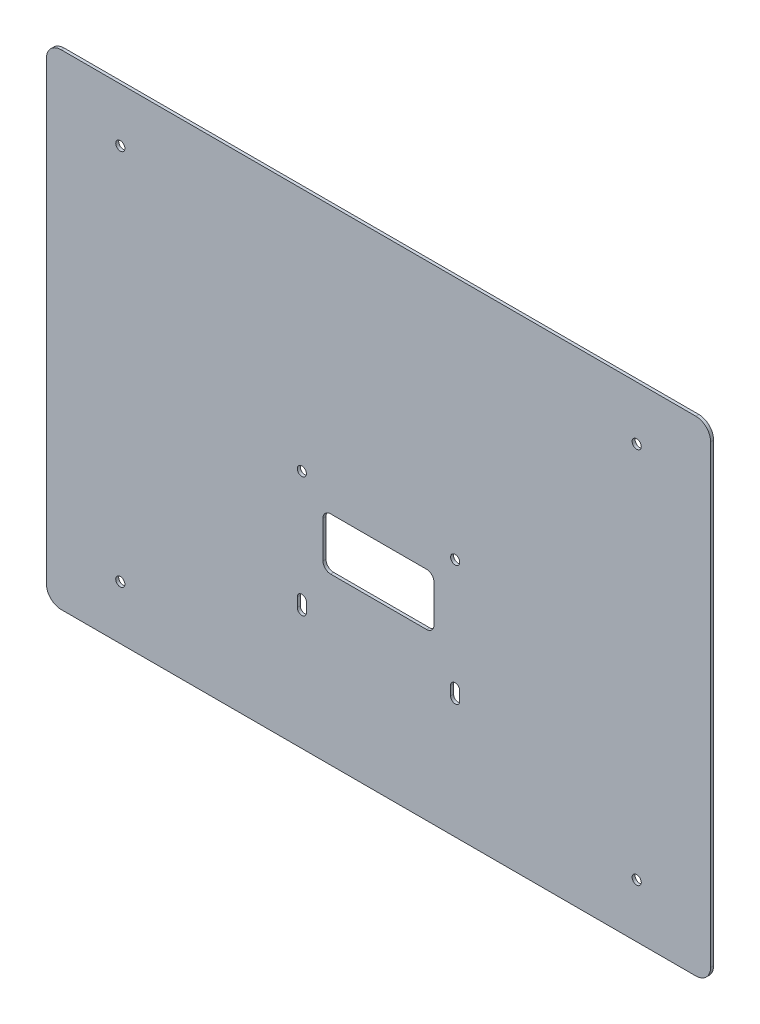
SolidWorks part; units mm, degrees
ref_plane "Front Plane" through (0, 0, 0) normal (0, 0, 1) x (1, 0, 0)
ref_plane "Top Plane" through (0, 0, 0) normal (0, 1, 0) x (1, 0, 0)
ref_plane "Right Plane" through (0, 0, 0) normal (1, 0, 0) x (0, 0, -1)
sketch "Sketch2" plane through (0, 0, 0) normal (0, 0, 1) x (1, 0, 0)
  line L1 (-225.24, 164.41) -> (225.24, 164.41)
  line L2 (-225.24, 164.41) -> (-225.24, -164.41)
  line L3 (-225.24, -164.41) -> (225.24, -164.41)
  line L4 (225.24, 164.41) -> (225.24, -164.41)
  line L5 (-225.24, 164.41) -> (225.24, -164.41) construction
  line L6 (-225.24, -164.41) -> (225.24, 164.41) construction
  point P0 (0, 0)
  dimension "Length 1" = 450.48
  dimension "Length 2" = 328.82
extrude "Boss-Extrude1" add sketch "Sketch2" along normal blind 2.032
sketch "Sketch3" plane through (0, 0, 2.032) normal (0, 0, 1) x (1, 0, 0)
  circle A0 centre (-175.117, 128.01) radius 3.1
  circle A1 centre (175.117, 128.01) radius 3.1
  circle A8 centre (-175.1171, -128.01) radius 3.1
  circle A9 centre (175.1169, -128.01) radius 3.1
  dimension "D1" = 6.2
extrude "Cut-Extrude1" cut sketch "Sketch3" against normal through all both and the other way through all
fillet "Fillet1" radius 10 4 edges at (-225.24, -164.41, 1.016) (225.24, -164.41, 1.016) (225.24, 164.41, 1.016) (-225.24, 164.41, 1.016)
sketch "Sketch4" [suppressed] plane through (0, 0, 0) normal (0, 0, -1) x (-1, 0, 0)
  circle A0 centre (-423.777, 128.01) radius 3.1
  circle A1 centre (423.777, 128.01) radius 3.1
  circle A2 centre (423.777, -128.01) radius 3.1
  circle A3 centre (-423.777, -128.01) radius 3.1
  dimension "D1" = 6.2
extrude "Cut-Extrude2" [suppressed] cut sketch "Sketch4" against normal through all both and the other way through all
fillet "Fillet2" [suppressed] radius 10
sketch "Sketch5" [suppressed] plane through (0, 0, 0) normal (0, 0, -1) x (-1, 0, 0)
  circle A0 centre (-175.117, -437.5) radius 3.1
  circle A1 centre (175.1169, -437.5) radius 3.1
  circle A2 centre (175.1169, 437.5) radius 3.1
  circle A3 centre (-175.117, 437.5) radius 3.1
  dimension "D1" = 6.2
extrude "Cut-Extrude3" [suppressed] cut sketch "Sketch5" against normal through all both and the other way through all
fillet "Fillet3" [suppressed] radius 10
sketch "Sketch6" [suppressed] plane through (0, 0, 0) normal (0, 0, -1) x (-1, 0, 0)
  circle A0 centre (175.9, -175.117) radius 3.1
  circle A1 centre (175.9, 175.117) radius 3.1
  circle A2 centre (-175.9, 175.117) radius 3.1
  circle A3 centre (-175.9, -175.117) radius 3.1
  dimension "D1" = 6.2
extrude "Cut-Extrude4" [suppressed] cut sketch "Sketch6" against normal through all both and the other way through all
sketch "Sketch7" [suppressed] plane through (0, 0, 2.032) normal (0, 0, 1) x (1, 0, 0)
  circle A0 centre (-139.6, -129.6148) radius 3.1
  circle A1 centre (-139.6, 138.5552) radius 3.1
  circle A2 centre (139.6, 151.166) radius 3.1
  circle A3 centre (139.6, -129.36) radius 3.1
  dimension "D1" = 6.2
extrude "Cut-Extrude5" [suppressed] cut sketch "Sketch7" against normal through all both and the other way through all
fillet "Fillet4" [suppressed] radius 10
sketch "Sketch8" plane through (0, 0, 2.032) normal (0, 0, 1) x (1, 0, 0)
  line L0 (-37.3761, -47.01) -> (-37.3761, -22.01) construction
  line L1 (32.5, -51.886) -> (-32.5, -51.886) construction
  line L2 (37.376, -22.01) -> (37.376, -47.01) construction
  line L3 (-32.5, -17.1339) -> (32.5, -17.1339) construction
  line L4 (-37.3761, -47.01) -> (-37.3761, -22.01) construction
  line L5 (32.5, -51.886) -> (-32.5, -51.886) construction
  line L6 (37.376, -22.01) -> (37.376, -47.01) construction
  line L7 (-32.5, -17.1339) -> (32.5, -17.1339) construction
  line L8 (-37.6761, -47.01) -> (-37.6761, -22.01)
  line L9 (32.5, -52.186) -> (-32.5, -52.186)
  line L10 (37.676, -22.01) -> (37.676, -47.01)
  line L11 (-32.5, -16.8339) -> (32.5, -16.8339)
  arc A0 (-37.3761, -47.01) -> (-32.5, -51.886) centre (-32.5, -47.01) ccw construction
  arc A1 (32.5, -51.886) -> (37.376, -47.01) centre (32.5, -47.01) ccw construction
  arc A2 (37.376, -22.01) -> (32.5, -17.1339) centre (32.5, -22.01) ccw construction
  arc A3 (-32.5, -17.1339) -> (-37.3761, -22.01) centre (-32.5, -22.01) ccw construction
  arc A4 (-37.3761, -47.01) -> (-32.5, -51.886) centre (-32.5, -47.01) ccw construction
  arc A5 (32.5, -51.886) -> (37.376, -47.01) centre (32.5, -47.01) ccw construction
  arc A6 (37.376, -22.01) -> (32.5, -17.1339) centre (32.5, -22.01) ccw construction
  arc A7 (-32.5, -17.1339) -> (-37.3761, -22.01) centre (-32.5, -22.01) ccw construction
  arc A8 (-32.5, -16.8339) -> (-37.6761, -22.01) centre (-32.5, -22.01) ccw
  arc A9 (-37.6761, -47.01) -> (-32.5, -52.186) centre (-32.5, -47.01) ccw
  arc A10 (32.5, -52.186) -> (37.676, -47.01) centre (32.5, -47.01) ccw
  arc A11 (37.676, -22.01) -> (32.5, -16.8339) centre (32.5, -22.01) ccw
  dimension "D1" = 0.3
extrude "Cut-Extrude6" cut sketch "Sketch8" against normal through all
sketch "Sketch9" plane through (0, 0, 2.032) normal (0, 0, 1) x (1, 0, 0)
  line L0 (-51.9979, -76.9078) -> (-51.9979, -83.1078) construction
  line L1 (-48.8979, -76.9078) -> (-48.8979, -83.1078)
  line L2 (-55.0979, -76.9078) -> (-55.0979, -83.1078)
  line L3 (51.9978, -76.9078) -> (51.9978, -83.1078) construction
  line L4 (55.0978, -76.9078) -> (55.0978, -83.1078)
  line L5 (48.8978, -76.9078) -> (48.8978, -83.1078)
  circle A0 centre (-51.9979, -1.5121) radius 3.1
  circle A1 centre (51.9978, -1.5121) radius 3.1
  circle A2 centre (-51.9979, -80.0078) radius 3.1 construction
  arc A3 (-48.8979, -76.9078) -> (-55.0979, -76.9078) centre (-51.9979, -76.9078) ccw
  arc A4 (-55.0979, -83.1078) -> (-48.8979, -83.1078) centre (-51.9979, -83.1078) ccw
  circle A5 centre (51.9978, -80.0078) radius 3.1 construction
  arc A6 (55.0978, -76.9078) -> (48.8978, -76.9078) centre (51.9978, -76.9078) ccw
  arc A7 (48.8978, -83.1078) -> (55.0978, -83.1078) centre (51.9978, -83.1078) ccw
  point P11 (-51.9979, -80.0078)
  point P17 (51.9978, -80.0078)
  dimension "D1" = 6.2
extrude "Cut-Extrude7" cut sketch "Sketch9" against normal through all
